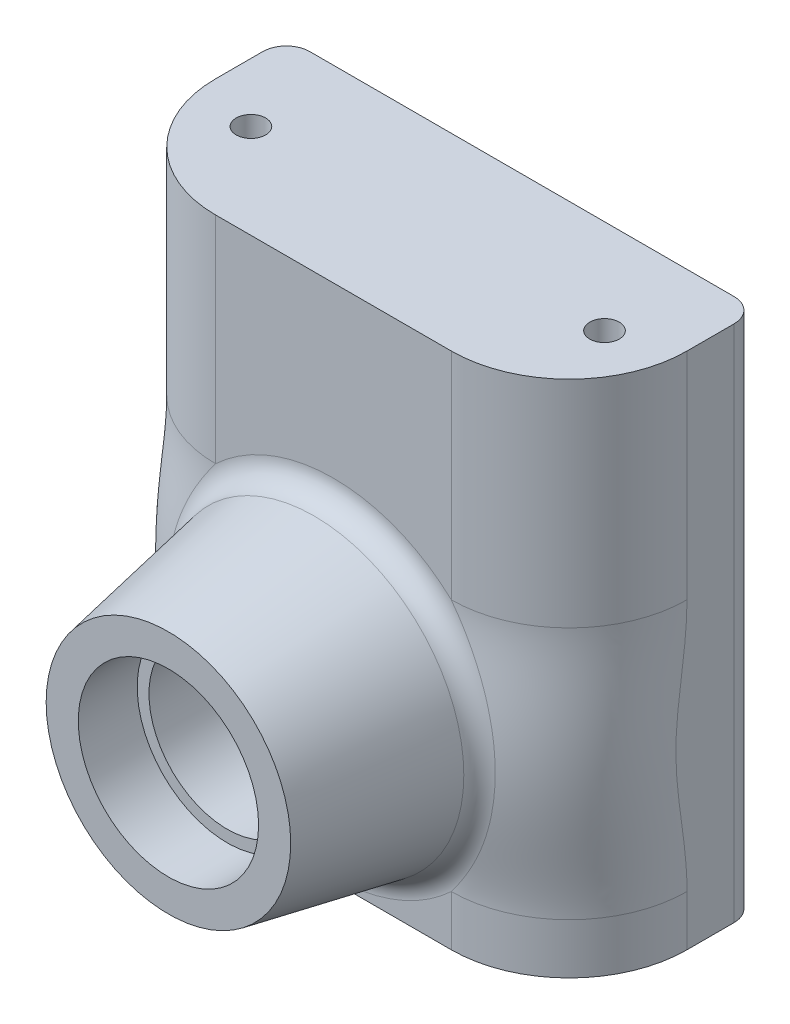
SolidWorks part; units mm, degrees
ref_plane "Спереди" through (0, 0, 0) normal (0, 0, 1) x (1, 0, 0)
ref_plane "Сверху" through (0, 0, 0) normal (0, 1, 0) x (1, 0, 0)
ref_plane "Справа" through (0, 0, 0) normal (1, 0, 0) x (0, 0, -1)
sketch "Эскиз1" plane through (0, 0, 0) normal (0, 0, 1) x (1, 0, 0)
  line L0 (0, 29) -> (0, -15) construction
  line L1 (-20, 29) -> (20, 29)
  line L2 (-20, 29) -> (-20, -15)
  line L3 (-20, -15) -> (20, -15)
  line L4 (20, 29) -> (20, -15)
  line L6 (-20, 0) -> (20, 0) construction
  dimension "D1" = 40
  dimension "D2" = 29
  dimension "D3" = 15
extrude "тело" add sketch "Эскиз1" against normal blind 16
sketch "Эскиз2" plane through (0, 0, 0) normal (0, 0, 1) x (1, 0, 0)
  circle A0 centre (0, 0) radius 10
  dimension "D1" = 20
extrude "утолщение оси" add sketch "Эскиз2" along normal blind 14
chamfer "Фаска2" distance 3 distance2 16 1 edges at (10, 0, 0) first distance on face at (10, 0, 0)
fillet "Скругление5" radius 2 1 edges at (13, 0, 0)
sketch "Эскиз7" plane through (0, 29, 0) normal (0, 1, 0) x (1, 0, 0)
  line L0 (-20, 8) -> (20, 8) construction
  line L1 (-20, 16) -> (-20, 0) construction
  line L2 (20, 16) -> (20, 0) construction
  line L3 (0, 16) -> (0, 0) construction
  line L4 (20, 16) -> (-20, 16) construction
  circle A0 centre (-15, 8) radius 1.25
  circle A1 centre (15, 8) radius 1.25
  dimension "D1" = 2.5
  dimension "D2" = 30
extrude "отверстия для шурупов" cut sketch "Эскиз7" against normal through all
fillet "Скругление7" radius 2 2 edges at (20, 7, -16) (-20, 7, -16)
sketch "Эскиз8" plane through (0, 0, 14) normal (0, 0, 1) x (1, 0, 0)
  circle A0 centre (0, 0) radius 7.65
  point P3 (0.7096, -3.1325)
  dimension "D1" = 15.3
extrude "углубление под подшипник" cut sketch "Эскиз8" against normal blind 5
sketch "Эскиз9" plane through (0, 0, -16) normal (0, 0, -1) x (-1, 0, 0)
  circle A0 centre (0, 0) radius 7.65
  point P3 (4.249, -1.8246)
  dimension "D1" = 15.3
extrude "углубление под подшипник с внутр стороны" cut sketch "Эскиз9" against normal blind 5
sketch "Эскиз4" plane through (0, 0, 14) normal (0, 0, 1) x (1, 0, 0)
  circle A0 centre (0, 0) radius 6.65
  circle A1 centre (0, 0) radius 7.65 construction
  dimension "D1" = 1
extrude "ось вращения" cut sketch "Эскиз4" against normal through all
fillet "Скругление8" radius 10 2 edges at (20, 7, 0) (-20, 7, 0)
